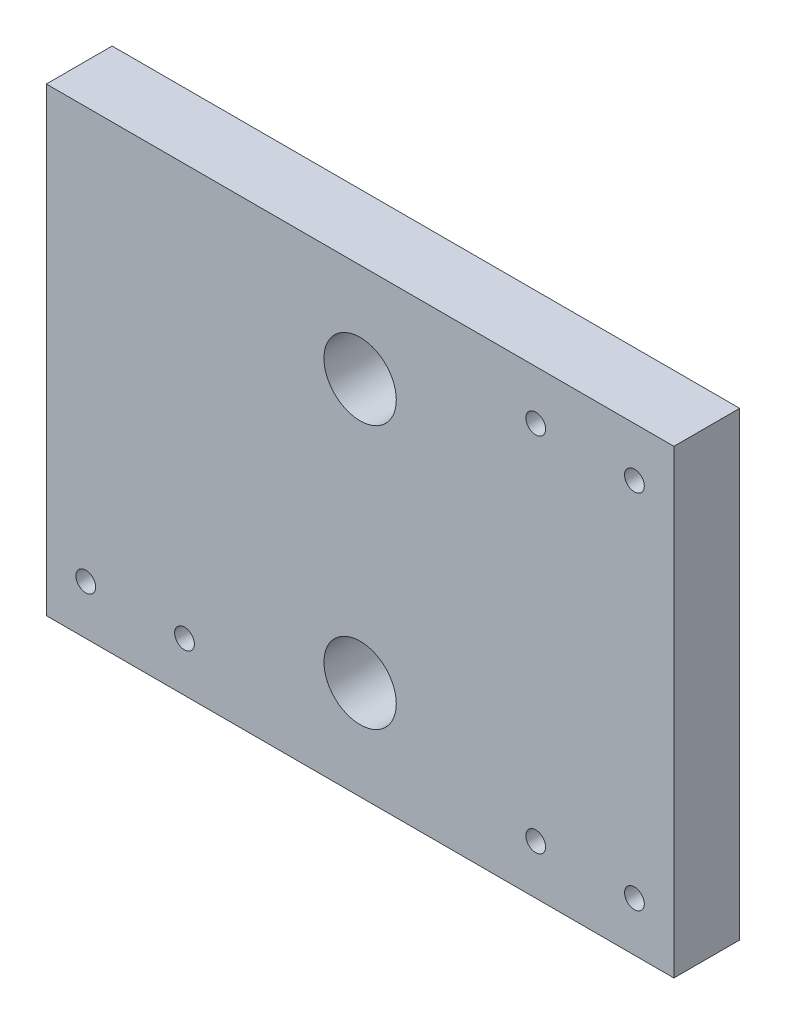
SolidWorks part; units mm, degrees
ref_plane "Front Plane" through (0, 0, 0) normal (0, 0, 1) x (1, 0, 0)
ref_plane "Top Plane" through (0, 0, 0) normal (0, 1, 0) x (1, 0, 0)
ref_plane "Right Plane" through (0, 0, 0) normal (1, 0, 0) x (0, 0, -1)
sketch "Sketch1" plane through (0, 0, 0) normal (0, 0, 1) x (1, 0, 0)
  line L0 (0, 0) -> (0, 40) construction
  line L2 (12.5, -15) -> (-12.5, -15)
  line L3 (12.5, -15) -> (12.5, 55)
  line L4 (12.5, 55) -> (-12.5, 55)
  line L5 (-12.5, -15) -> (-12.5, 55)
  line L6 (12.5, -15) -> (-12.5, 55) construction
  line L7 (12.5, 55) -> (-12.5, -15) construction
  circle A0 centre (0, 40) radius 7.9375
  circle A1 centre (0, 0) radius 7.9375
  point P5 (0, 20)
  dimension "D2" = 15.875
  dimension "D1" = 40
  dimension "D3" = 70
  dimension "D4" = 25
extrude "Boss-Extrude1" add sketch "Sketch1" along normal blind 10
sketch "Sketch2" plane through (0, 0, 10) normal (0, 0, 1) x (1, 0, 0)
  line L0 (12.5, 55) -> (-12.5, 55) construction
  line L1 (-47.7, 55) -> (-8.2, 55)
  line L3 (-47.7, -15) -> (-8.2, -15)
  line L4 (-8.2, 55) -> (-8.2, 35.0594)
  line L5 (-8.2, 35.0594) -> (-8.2, 32.231)
  line L6 (8.2, 35.0594) -> (8.2, 32.231)
  line L7 (-12.5, -15) -> (12.5, -15) construction
  line L8 (-8.2, 32.231) -> (-8.2, 4.0594)
  line L9 (-8.2, 1.231) -> (-8.2, 4.0594)
  line L16 (8.2, 1.231) -> (8.2, 4.0594)
  line L24 (8.2, 55) -> (8.2, 35.0594)
  line L25 (47.7, -15) -> (8.2, -15)
  line L27 (47.7, 55) -> (8.2, 55)
  line L28 (-47.7, 55) -> (-47.7, -15)
  line L29 (47.7, 55) -> (47.7, -15)
  line L31 (-8.2, 1.231) -> (-8.2, -15)
  line L32 (8.2, 1.231) -> (8.2, -15)
  line L33 (8.2, 32.231) -> (8.2, 4.0594)
extrude "Boss-Extrude2" add sketch "Sketch2" against normal up to surface (10 mm away) up to face at (0, 20, 0)
sketch "Sketch3" plane through (0, 0, 10) normal (0, 0, 1) x (1, 0, 0)
  circle A0 centre (0, 40) radius 5.5
  circle A1 centre (0, 0) radius 5.5
  circle A2 centre (0, 40) radius 7.9375 construction
  circle A3 centre (0, 40) radius 7.9375
  circle A4 centre (0, 0) radius 7.9375 construction
  circle A5 centre (0, 0) radius 7.9375
  dimension "D1" = 11
extrude "Boss-Extrude3" add sketch "Sketch3" against normal blind 8
sketch "Sketch4" plane through (0, 0, 0) normal (0, 0, -1) x (-1, 0, 0)
  circle A0 centre (-41.7, 47.5) radius 1.5 construction
  circle A1 centre (-26.7, 47.5) radius 1.5 construction
  circle A2 centre (-41.7, -7.5) radius 1.5 construction
  circle A3 centre (-26.7, -7.5) radius 1.5 construction
  circle A4 centre (41.7, -7.5) radius 1.5 construction
  circle A5 centre (26.7, -7.5) radius 1.5 construction
  circle A6 centre (-41.7, 47.5) radius 1.5
  circle A7 centre (-26.7, 47.5) radius 1.5
  circle A8 centre (-41.7, -7.5) radius 1.5
  circle A9 centre (-26.7, -7.5) radius 1.5
  circle A10 centre (41.7, -7.5) radius 1.5
  circle A11 centre (26.7, -7.5) radius 1.5
extrude "Cut-Extrude1" cut sketch "Sketch4" against normal through all
